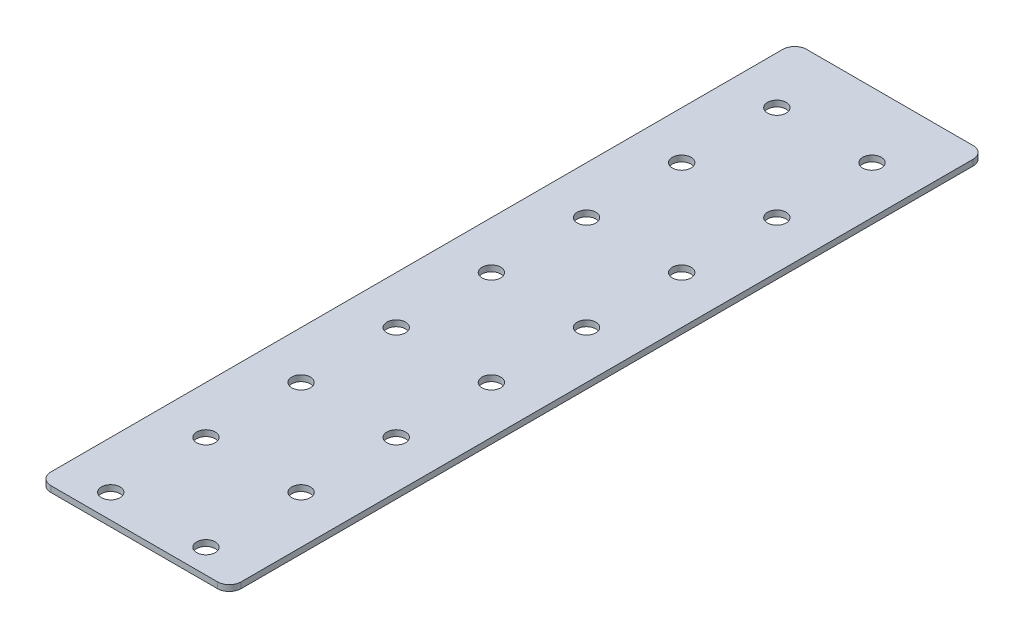
SolidWorks part; units mm, degrees
material "6061-T6 (SS)"
ref_plane "Front Plane" through (0, 0, 0) normal (0, 0, 1) x (1, 0, 0)
ref_plane "Top Plane" through (0, 0, 0) normal (0, 1, 0) x (1, 0, 0)
ref_plane "Right Plane" through (0, 0, 0) normal (1, 0, 0) x (0, 0, -1)
sketch "Sketch1" plane through (0, 0, 0) normal (0, 1, 0) x (1, 0, 0)
  line L1 (0, 0) -> (50.8, 0)
  line L2 (0, 0) -> (0, 201.7201)
  line L3 (0, 201.7201) -> (50.8, 201.7201)
  line L4 (50.8, 0) -> (50.8, 201.7201)
  circle A0 centre (12.7, 6.4576) radius 2.4892
  circle A1 centre (12.7, 31.8576) radius 2.4892
  circle A2 centre (12.7, 57.2576) radius 2.4892
  circle A3 centre (12.7, 82.6576) radius 2.4892
  circle A4 centre (12.7, 108.0576) radius 2.4892
  circle A5 centre (12.7, 133.4576) radius 2.4892
  circle A6 centre (38.1, 31.8576) radius 2.4892
  circle A7 centre (38.1, 57.2576) radius 2.4892
  circle A8 centre (38.1, 82.6576) radius 2.4892
  circle A9 centre (38.1, 108.0576) radius 2.4892
  circle A10 centre (38.1, 133.4576) radius 2.4892
  circle A11 centre (38.1, 6.4576) radius 2.4892
  circle A12 centre (12.7, 158.8576) radius 2.4892
  circle A13 centre (12.7, 184.2576) radius 2.4892
  circle A14 centre (38.1, 158.8576) radius 2.4892
  circle A15 centre (38.1, 184.2576) radius 2.4892
  dimension "D3" = 4.9784
  dimension "D4" = 12.7
  dimension "D5" = 6.4576
  dimension "D1" = 50.8
  dimension "D2" = 201.7201
  dimension "D8" = 25.4
  dimension "D9" = 25.4
  dimension "D6" = 8
  dimension "D7" = 2
extrude "Boss-Extrude1" add sketch "Sketch1" along normal blind 1.5875
fillet "Fillet1" radius 3.175 4 edges at (0, 0.7937, -201.7201) (50.8, 0.7937, -201.7201) (0, 0.7937, 0) (50.8, 0.7937, 0)
